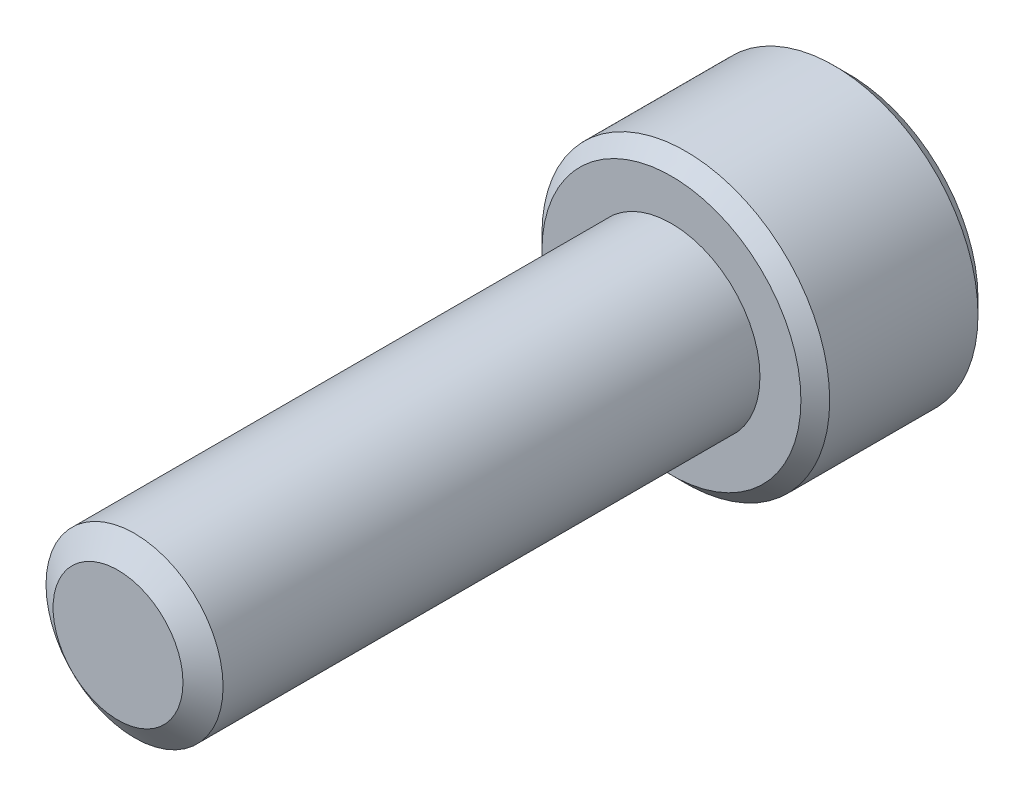
SolidWorks part; units mm, degrees
other "DetailItem1"
ref_plane "Front Plane" through (0, 0, 0) normal (0, 0, 1) x (1, 0, 0)
ref_plane "Top Plane" through (0, 0, 0) normal (0, 1, 0) x (1, 0, 0)
ref_plane "Right Plane" through (0, 0, 0) normal (1, 0, 0) x (0, 0, -1)
sketch "Sketch1" plane through (0, 0, 0) normal (0, 0, 1) x (1, 0, 0)
  circle A0 centre (0, 0) radius 4
  dimension "OD" = 8
extrude "Extrude1" add sketch "Sketch1" against normal blind 25
sketch "Sketch2" plane through (0, 0, 0) normal (0, 0, 1) x (1, 0, 0)
  circle A0 centre (0, 0) radius 4 construction
  circle A1 centre (0, 0) radius 4
curve "Helix/Spiral1" pitch 1.25 height 26.25 turns 21 parameters "pitch"=1.25
sketch "Sketch3" plane through (0, 0, 0) normal (1, 0, 0) x (0, 0, -1)
  line L0 (-1.0938, 4) -> (-0.625, 3.1881)
  line L1 (-0.625, 3.1881) -> (-0.4688, 3.1881)
  line L2 (-0.4688, 3.1881) -> (0, 4)
  line L3 (-1.0938, 4) -> (0, 4)
  line L4 (-0.5469, 4) -> (-0.5469, 3.1881) construction
  line L5 (-0.8594, 3.5941) -> (-0.2344, 3.5941) construction
  line L6 (0, 4) -> (0, -4) construction
  dimension "D1" = 0.1562
  dimension "D2" = 0.625
  dimension "D3" = 60
sweep "Cut-Sweep1" [suppressed] cut profiles "Sketch3" path "Helix/Spiral1"
sketch "Sketch4" plane through (0, 0, 0) normal (1, 0, 0) x (0, 0, -1)
  line L0 (0.7464, 4) -> (0, 2.9341)
  line L1 (0, 2.9341) -> (0, 4)
  line L2 (0.7464, 4) -> (0, 4)
  line L3 (-1.0938, 4) -> (0, 4) construction
  line L4 (0, 0) -> (7.0209, 0) construction
  dimension "D1" = 55
  dimension "D2" = 0.254
revolve "Cut-Revolve1" cut sketch "Sketch4" angle 360 about L4
sketch "Sketch6" plane through (0, 0, -25) normal (0, 0, -1) x (-1, 0, 0)
  circle A0 centre (0, 0) radius 6.5
  dimension "head dia" = 13
extrude "Extrude2" add sketch "Sketch6" along normal blind 8
sketch "Sketch7" plane through (0, 0, -33) normal (0, 0, -1) x (-1, 0, 0)
  line L1 (0, 3.4641) -> (-3, 1.7321)
  line L2 (-3, 1.7321) -> (-3, -1.7321)
  line L3 (-3, -1.7321) -> (0, -3.4641)
  line L4 (0, -3.4641) -> (3, -1.7321)
  line L5 (3, -1.7321) -> (3, 1.7321)
  line L6 (3, 1.7321) -> (0, 3.4641)
  circle A0 centre (0, 0) radius 3 construction
  dimension "hex dia" = 6
extrude "Cut-Extrude1" cut sketch "Sketch7" against normal blind 4.5
sketch "Sketch8" plane through (0, 0, -33) normal (0, 0, -1) x (-1, 0, 0)
  circle A0 centre (0, 0) radius 3.4641
extrude "Cut-Extrude2" cut sketch "Sketch8" against normal through all draft 45
chamfer "Chamfer1" distance 0.65 angle 45 2 edges at (-6.5, 0, -33) (-6.5, 0, -25)
sketch "Sketch10" plane through (0, 0, -25) normal (0, 0, 1) x (1, 0, 0)
  circle A1 centre (0, 0) radius 4
  circle A2 centre (0, 0) radius 4
  dimension "D1" = 0
ref_plane "Plane1" through (0, 0, 0) normal (0, 0, 1) x (1, 0, 0)
extrude "partial thread" [suppressed] add sketch "Sketch10" along normal up to surface (57 mm away) separate body up to plane "Plane1"
chamfer "Chamfer2" [suppressed] distance 0.16 angle 45
combine bodies "Combine1" [suppressed] operation type add bodies to combine 107 108
sketch "Sketch9" plane through (0, 0, 0) normal (1, 0, 0) x (0, 0, -1)
  line L0 (0, 4) -> (0, -4) construction
  line L1 (3.125, 4) -> (3.125, -4) construction
  dimension "D1" = 3.125
equation "\"D3@Helix/Spiral1\" = \"screw length@Extrude1\"+\"pitch@Helix/Spiral1\""
equation "\"D1@Sketch3\" = \"pitch@Helix/Spiral1\"*.125"
equation "\"D2@Sketch3\" = \"pitch@Helix/Spiral1\"*.5"
equation "\"D1@Cut-Extrude1\" = \"hex dia@Sketch7\"*.75"
equation "\"D1@Chamfer1\" = \"head dia@Sketch6\"*.05"
equation "\"D1@Sketch9\" = \"pitch@Helix/Spiral1\"*2.5"
equation "\"D1@Chamfer2\"=\"OD@Sketch1\"*.02"
